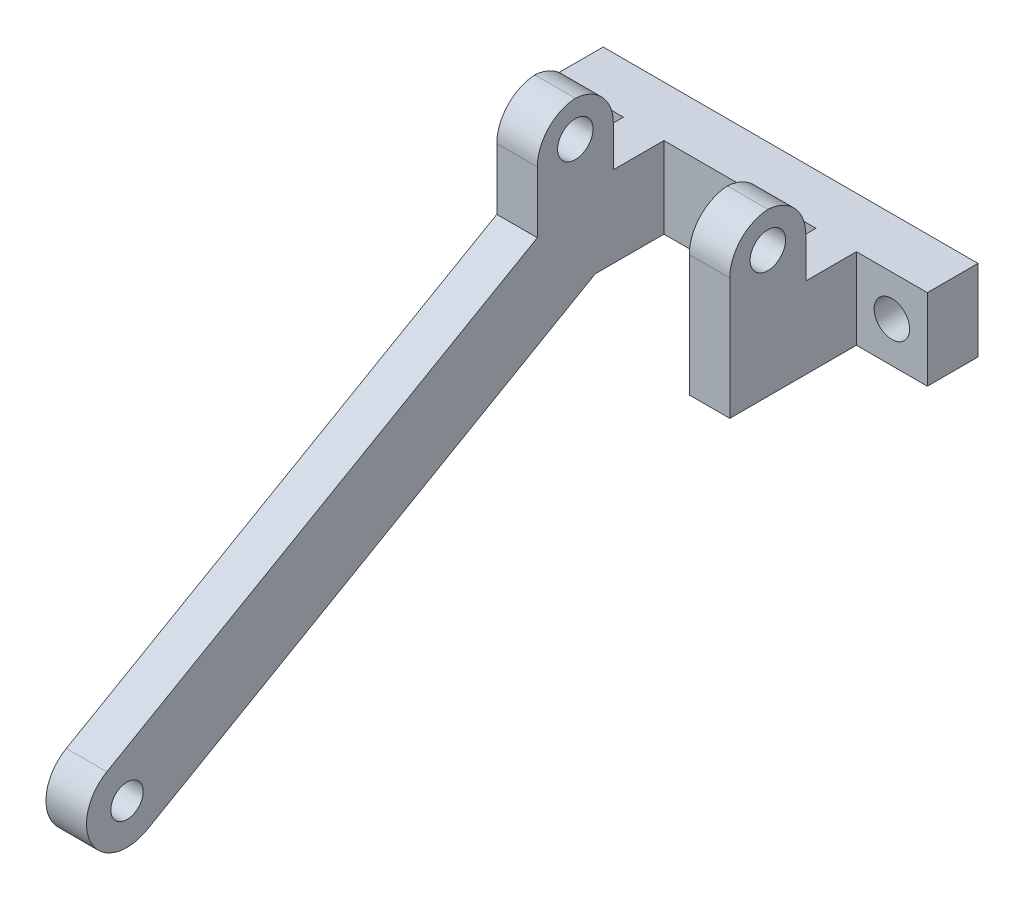
SolidWorks part; units mm, degrees
ref_plane "Front Plane" through (0, 0, 0) normal (0, 0, 1) x (1, 0, 0)
ref_plane "Top Plane" through (0, 0, 0) normal (0, 1, 0) x (1, 0, 0)
ref_plane "Right Plane" through (0, 0, 0) normal (1, 0, 0) x (0, 0, -1)
sketch "Sketch1" plane through (0, 0, 0) normal (0, 0, 1) x (1, 0, 0)
  line L0 (15, 0) -> (-15, 0) construction
  line L1 (-18.5, 4) -> (18.5, 4)
  line L2 (-18.5, 4) -> (-18.5, -4)
  line L3 (-18.5, -4) -> (18.5, -4)
  line L4 (18.5, 4) -> (18.5, -4)
  line L5 (-18.5, 4) -> (18.5, -4) construction
  line L6 (-18.5, -4) -> (18.5, 4) construction
  line L7 (0, -4) -> (0, 4) construction
  circle A0 centre (-15, 0) radius 1.75
  circle A1 centre (15, 0) radius 1.75
  point P0 (0, 0)
  point P12 (0, 0)
  dimension "D3" = 3.5
  dimension "D1" = 37
  dimension "D2" = 8
  dimension "D4" = 15
extrude "Boss-Extrude1" add sketch "Sketch1" along normal blind 5
sketch "Sketch2" plane through (0, 0, 5) normal (0, 0, 1) x (1, 0, 0)
  line L0 (0, 4) -> (0, -4) construction
  line L1 (18.5, 4) -> (-18.5, 4) construction
  line L2 (-18.5, -4) -> (18.5, -4) construction
  line L3 (11.5, -4) -> (7.5, 4) construction
  line L4 (-11.5, 4) -> (-7.5, 4)
  line L5 (-11.5, 4) -> (-11.5, -4)
  line L6 (-11.5, -4) -> (-7.5, -4)
  line L7 (-7.5, 4) -> (-7.5, -4)
  line L8 (-11.5, 4) -> (-7.5, -4) construction
  line L9 (-11.5, -4) -> (-7.5, 4) construction
  line L10 (11.5, 4) -> (7.5, -4) construction
  line L11 (7.5, 4) -> (7.5, -4)
  line L12 (11.5, -4) -> (7.5, -4)
  line L13 (11.5, 4) -> (11.5, -4)
  line L14 (11.5, 4) -> (7.5, 4)
  point P6 (-9.5, 0)
  point P15 (9.5, 0)
  dimension "D1" = 7.5
  dimension "D2" = 4
extrude "Boss-Extrude2" add sketch "Sketch2" along normal blind 12.5
sketch "Sketch4" plane through (0, 4, 0) normal (0, 1, 0) x (1, 0, 0)
  line L0 (-7.5, -17.5) -> (-7.5, -5) construction
  line L1 (-11.5, -17.5) -> (-7.5, -17.5)
  line L2 (-11.5, -17.5) -> (-11.5, -10)
  line L3 (-11.5, -10) -> (-7.5, -10)
  line L4 (-7.5, -17.5) -> (-7.5, -10)
  line L5 (0, 0) -> (0, -5) construction
  line L6 (7.5, -5) -> (-7.5, -5) construction
  line L7 (7.5, -17.5) -> (7.5, -10)
  line L8 (11.5, -10) -> (7.5, -10)
  line L9 (11.5, -17.5) -> (11.5, -10)
  line L10 (11.5, -17.5) -> (7.5, -17.5)
  dimension "D1" = 7.5
extrude "Boss-Extrude3" add sketch "Sketch4" along normal blind 8
sketch "Sketch3" plane through (-11.5, 0, 0) normal (-1, 0, 0) x (0, 0, 1)
  line L0 (10, 8.5) -> (17.5, 8.5) construction
  line L4 (10, 12) -> (10, 4) construction
  line L5 (17.5, 12) -> (17.5, -4) construction
  line L6 (13.75, 8.5) -> (13.75, 12) construction
  line L7 (10, 12) -> (17.5, 12) construction
  circle A0 centre (13.75, 8.5) radius 1.75
  dimension "D1" = 3.5
  dimension "D2" = 8.5
extrude "Cut-Extrude1" cut sketch "Sketch3" against normal through all
fillet "Fillet1" radius 4 4 edges at (-9.5, 12, 10) (9.5, 12, 10) (9.5, 12, 17.5) (-9.5, 12, 17.5)
sketch "Sketch5" plane through (-7.5, 0, 0) normal (1, 0, 0) x (0, 0, -1)
  line L0 (-10, 8) -> (-10, 4) construction
  line L1 (-10, 6.5) -> (-13, 6.5)
  line L2 (-10, 6.5) -> (-10, 1.5)
  line L3 (-10, 1.5) -> (-13, 1.5)
  line L4 (-13, 6.5) -> (-13, 1.5)
  line L5 (-10, 4) -> (-5, 4) construction
  dimension "D1" = 3
  dimension "D2" = 5
  dimension "D3" = 2.5
extrude "Boss-Extrude4" [suppressed] add sketch "Sketch5" along normal up to next
sketch "Sketch6" plane through (-11.5, 0, 0) normal (-1, 0, 0) x (0, 0, 1)
  line L0 (56.0113, -29.4012) -> (11.7824, -4)
  line L1 (17.5, -4) -> (5, -4) construction
  line L2 (11.7824, -4) -> (17.5, 1.9418)
  line L3 (13.75, 8.5) -> (58.0033, -25.9326) construction
  line L4 (17.5, 1.9418) -> (59.9954, -22.4639)
  line L5 (59.9954, -22.4639) -> (56.0113, -29.4012) construction
  line L6 (13.75, 8.5) -> (13.75, -4) construction
  line L7 (17.5, 8) -> (17.5, -4) construction
  circle A0 centre (58.0033, -25.9326) radius 1.6
  arc A1 (56.0113, -29.4012) -> (59.9954, -22.4639) centre (58.0033, -25.9326) ccw
  dimension "D1" = 3.2
  dimension "D2" = 8
  dimension "D3" = 52.114
  dimension "D4" = 56.071
  dimension "D5" = 1.9676
extrude "Boss-Extrude5" add sketch "Sketch6" against normal up to surface (4 mm away) up to face at (-7.5, 6.75, 13.75)
equation "\"X-ROD-SPACING\"=45"
equation "\"Y-ROD-SPACING\"=75"
equation "\"Z-ROD-SPACING\"=17.5"
equation "\"Y-BED-OFFSET\"=2"
equation "\"Y-BED-ROD-INSET\"=3.5"
equation "\"Y-BED-SCREW-SPACING\"=209"
equation "\"Y-BED-SCREW-CUTOUT-SLOT-HEIGHT\"=2"
equation "\"T-SLOT-NUT-FILLET-RADIUS\"=0.25"
equation "\"T-SLOT-SCREW-SHAFT-RADIUS\"=1.75"
equation "\"T-SLOT-SCREW-SHAFT-CUTOUT-LENGTH\"=10.5"
equation "\"T-SLOT-NUT-DEPTH\"=4.2"
equation "\"T-SLOT-NUT-WIDTH\"=3"
equation "\"T-SLOT-NUT-END-DISTANCE\"=8"
equation "\"ACRYLIC-THICKNESS\"=10"
equation "\"ACRYLIC-THICKNESS2\"=4.5"
equation "\"ACRYLIC-TAB-CUTOUT-SIZE\"=\"ACRYLIC-THICKNESS\"+\"ACRYLIC-TAB-TOLERANCE\"*2"
equation "\"ACRYLIC-TAB-TOLERANCE\"=.1"
equation "\"ACRYLIC-TAB-WIDTH\"=\"ACRYLIC-THICKNESS\""
equation "\"ACRYLIC-M3-HOLE\"=3.1"
equation "\"SMOOTHROD-CAP-SCREW-DISTANCE\"=20"
equation "\"FRAME-WIDTH-INNER\"=370"
equation "\"NEMA17-HOLE-SPACING\"=31"
equation "\"NEMA17-CENTRAL-CUTOUT\"=22.5"
equation "\"Z-BRACKET-REACH\"=55"
equation "\"Z-ROD-INSET\"=16"
equation "\"TOP-BRACKET-SPACING\"=40"
equation "\"SMOOTHROD-X-LENGTH\"=350"
equation "\"SMOOTHROD-Y-LENGTH\"=350"
equation "\"SMOOTHROD-Z-LENGTH\"=350"
equation "\"SMOOTHROD-TIGHTENING-HEADROOM\"=.25"
equation "\"LEADSCREW-Z-LENGTH\"=300"
equation "\"SCREW-LENGTH-FRAME\"=\"ACRYLIC-THICKNESS\" + 10"
equation "\"SCREW-LENGTH-MOTOR\"=\"ACRYLIC-THICKNESS\" + 5"
equation "\"SCREW-LENGTH-EXTRUDER\"=28"
equation "\"SCREW-HEAD-RADIUS\"=6"
equation "\"PRINTED-X-SMOOTHROD-DIAMETER\"=8.2"
equation "\"PRINTED-X-SMOOTHROD-CUTOUT\"=10"
equation "\"PRINTED-X-BASE-HEIGHT\"=10"
equation "\"PRINTED-LM8UU-CUTOUT-SIZE\"=15.25"
equation "\"PRINTED-LM8UU-CUTOUT-LENGTH\"=24.5"
equation "\"PRINTED-X-IDLER-HEIGHT\"=16"
equation "\"PSU-MOUNTING-WIDTH\"=95"
equation "\"PSU-MOUNTING-HEIGHT\"=177"
equation "\"Y-BELT-TO-ROD-DISTANCE\"=20"
equation "\"SPOOL-HOLDER-ROD-SPACING\"=150"
equation "\"ACRYLIC-X-CARRIAGE-WIDTH\"=55"
equation "\"ACRYLIC-X-CARRIAGE-HEIGHT\"=75"
equation "\"ACRYLIC-X-CARRIAGE-LM8UU-CUTOUT-WIDTH\"=24.25"
equation "\"ACRYLIC-X-CARRIAGE-LM8UU-CUTOUT-HEIGHT\"=11.5"
equation "\"ACRYLIC-X-CARRIAGE-SCREW-SPACING-X\"=15"
equation "\"ACRYLIC-X-CARRIAGE-SCREW-SPACING-Y\"=33"
equation "\"ACRYLIC-X-CARRIAGE-CENTER-TAB-SPACING\"=14"
equation "\"ACRYLIC-X-CARRIAGE-EXTRUDER-OFFSET\"=26"
equation "\"ACRYLIC-X-CARRIAGE-EXTRUDER-ANGLE\"=90"
equation "\"ACRYLIC-X-CARRIAGE-EXTRUDER-SHELF-DEPTH\"=\"ACRYLIC-X-CARRIAGE-EXTRUDER-OFFSET\" + 28"
equation "\"ACRYLIC-X-CARRIAGE-EXTRUDER-BRACE-SPACING\"=23"
equation "\"ACRYLIC-X-CARRIAGE-EXTRUDER-BRACE-TAB-OFFSET\"=20"
equation "\"ACRYLIC-X-CARRIAGE-EXTRUDER-BRACE-HEIGHT\"=35"
equation "\"ACRYLIC-X-CARRIAGE-EXTRUDER-BRACE-SCREW-SPACING\"=22"
equation "\"ACRYLIC-X-CARRIAGE-DUAL-WIDTH-MULTIPLIER\"=1.65"
equation "\"ACRYLIC-X-CARRIAGE-DUAL-HOTEND-SPACING\"=42"
equation "\"ACRYLIC-X-CARRIAGE-DUAL-WIDTH\"=103"
equation "\"ACRYLIC-X-CARRIAGE-DUAL-HOTEND-SEPARATION\"=35"
equation "\"ACRYLIC-X-CARRIAGE-DUAL-MOUNT-PLATE-DEPTH\"=76"
equation "\"ACRYLIC-X-CARRIAGE-DUAL-MOUNT-BRACE-WIDTH\"=45"
equation "\"ACRYLIC-X-CARRIAGE-DUAL-MOUNT-SCREW-WIDTH\"=40"
equation "\"D3@Sketch1\"=3.5"
equation "\"PRINTED-M3-HOLE\"=3.5"
equation "\"BLOWER-FAN-WIDTH\"=15"
equation "\"D1@Sketch2\"=\"BLOWER-FAN-WIDTH\"/2"
